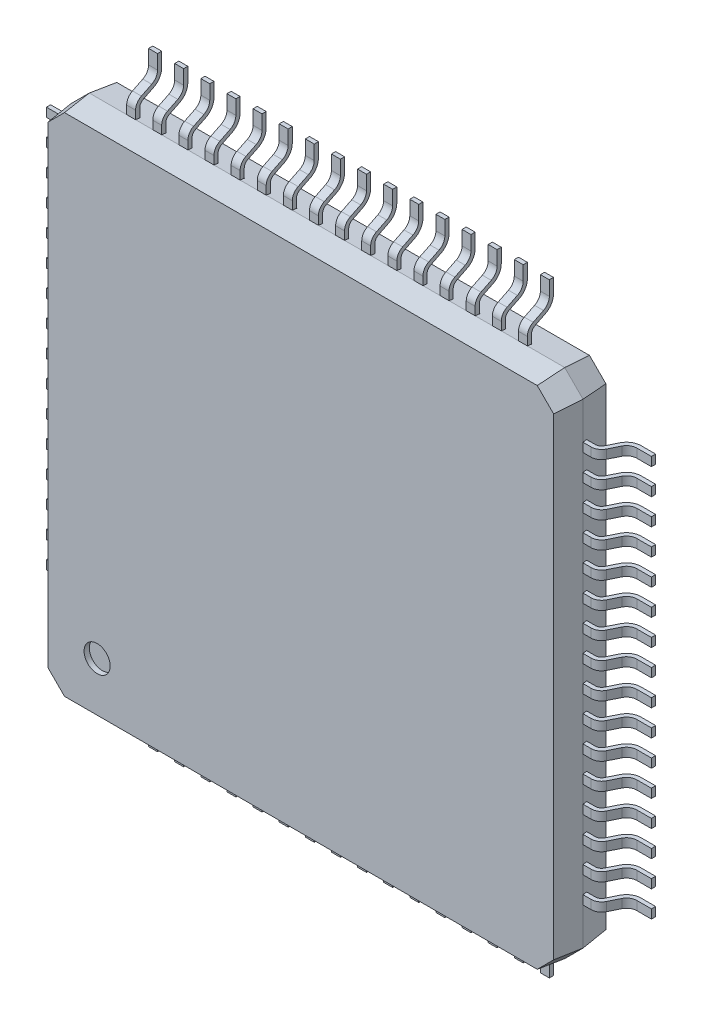
SolidWorks part; units mm, degrees
ref_plane "Front Plane" through (0, 0, 0) normal (0, 0, 1) x (1, 0, 0)
ref_plane "Top Plane" through (0, 0, 0) normal (0, 1, 0) x (1, 0, 0)
ref_plane "Right Plane" through (0, 0, 0) normal (1, 0, 0) x (0, 0, -1)
sketch "Sketch1" plane through (0, 0, 0) normal (0, 0, 1) x (1, 0, 0)
  line L0 (-4.55, 4.9) -> (-4.9, 4.55)
  line L1 (-4.55, 4.9) -> (4.55, 4.9)
  line L2 (-4.9, 4.55) -> (-4.9, -4.55)
  line L3 (-4.55, -4.9) -> (4.55, -4.9)
  line L4 (4.9, 4.55) -> (4.9, -4.55)
  line L5 (-4.9, -4.55) -> (-4.55, -4.9)
  line L6 (4.55, -4.9) -> (4.9, -4.55)
  line L7 (4.55, 4.9) -> (4.9, 4.55)
  point P0 (0, 0)
  point P1 (-4.9, 4.9)
  point P3 (4.9, -4.9)
  point P4 (-4.9, -4.9)
  point P5 (4.9, 4.9)
  dimension "D1" = 0.35
  dimension "D2" = 0.35
  dimension "D3" = 0.35
  dimension "D4" = 0.35
  dimension "D5" = 0.35
  dimension "D6" = 0.35
  dimension "D7" = 0.35
  dimension "D8" = 0.35
extrude "Extrude1" add sketch "Sketch1" along normal blind 1
chamfer "Chamfer1" distance 0.5 angle 7 8 edges at (0, 4.9, 1) (-4.725, 4.725, 1) (-4.9, 0, 1) (-4.725, -4.725, 1) (0, -4.9, 1) (4.725, -4.725, 1) (4.9, 0, 1) (4.725, 4.725, 1)
chamfer "Chamfer4" distance 0.5 angle 7 8 edges at (4.725, -4.725, 0) (4.9, 0, 0) (4.725, 4.725, 0) (0, 4.9, 0) (0, -4.9, 0) (-4.725, -4.725, 0) (-4.725, 4.725, 0) (-4.9, 0, 0)
sketch "Sketch2" plane through (0, 0, 1) normal (0, 0, 1) x (1, 0, 0)
  circle A0 centre (-3.9, -3.9) radius 0.25
extrude "Extrude2" cut sketch "Sketch2" against normal blind 0.1
sketch "Sketch4" plane through (0, 0, 0) normal (0, 0, -1) x (-1, 0, 0)
  line L0 (-3.3358, -4.8899) -> (-3.165, -4.8899)
  line L1 (0, 0) -> (0, 5.3794) construction
  line L2 (-5.7946, 0) -> (6, 0) construction
  line L3 (-3.3358, -4.8899) -> (-3.3358, -5.7873)
  line L4 (-3.3358, -5.7873) -> (-3.165, -5.7873)
  line L5 (-3.165, -4.8899) -> (-3.165, -5.7873)
  line L7 (-2.8358, -4.8899) -> (-2.665, -4.8899)
  line L8 (-2.8358, -4.8899) -> (-2.8358, -5.7873)
  line L9 (-2.8358, -5.7873) -> (-2.665, -5.7873)
  line L10 (-2.665, -4.8899) -> (-2.665, -5.7873)
  line L11 (-2.3358, -4.8899) -> (-2.165, -4.8899)
  line L12 (-2.3358, -4.8899) -> (-2.3358, -5.7873)
  line L13 (-2.3358, -5.7873) -> (-2.165, -5.7873)
  line L14 (-2.165, -4.8899) -> (-2.165, -5.7873)
  line L15 (-1.8358, -4.8899) -> (-1.665, -4.8899)
  line L16 (-1.8358, -4.8899) -> (-1.8358, -5.7873)
  line L17 (-1.8358, -5.7873) -> (-1.665, -5.7873)
  line L18 (-1.665, -4.8899) -> (-1.665, -5.7873)
  line L19 (-1.3358, -4.8899) -> (-1.165, -4.8899)
  line L20 (-1.3358, -4.8899) -> (-1.3358, -5.7873)
  line L21 (-1.3358, -5.7873) -> (-1.165, -5.7873)
  line L22 (-1.165, -4.8899) -> (-1.165, -5.7873)
  line L23 (-0.8358, -4.8899) -> (-0.665, -4.8899)
  line L24 (-0.8358, -4.8899) -> (-0.8358, -5.7873)
  line L25 (-0.8358, -5.7873) -> (-0.665, -5.7873)
  line L26 (-0.665, -4.8899) -> (-0.665, -5.7873)
  line L27 (-0.3358, -4.8899) -> (-0.165, -4.8899)
  line L28 (-0.3358, -4.8899) -> (-0.3358, -5.7873)
  line L29 (-0.3358, -5.7873) -> (-0.165, -5.7873)
  line L30 (-0.165, -4.8899) -> (-0.165, -5.7873)
  line L31 (0.1642, -4.8899) -> (0.335, -4.8899)
  line L32 (0.1642, -4.8899) -> (0.1642, -5.7873)
  line L33 (0.1642, -5.7873) -> (0.335, -5.7873)
  line L34 (0.335, -4.8899) -> (0.335, -5.7873)
  line L35 (0.6642, -4.8899) -> (0.835, -4.8899)
  line L36 (0.6642, -4.8899) -> (0.6642, -5.7873)
  line L37 (0.6642, -5.7873) -> (0.835, -5.7873)
  line L38 (0.835, -4.8899) -> (0.835, -5.7873)
  line L39 (1.1642, -4.8899) -> (1.335, -4.8899)
  line L40 (1.1642, -4.8899) -> (1.1642, -5.7873)
  line L41 (1.1642, -5.7873) -> (1.335, -5.7873)
  line L42 (1.335, -4.8899) -> (1.335, -5.7873)
  line L43 (1.6642, -4.8899) -> (1.835, -4.8899)
  line L44 (1.6642, -4.8899) -> (1.6642, -5.7873)
  line L45 (1.6642, -5.7873) -> (1.835, -5.7873)
  line L46 (1.835, -4.8899) -> (1.835, -5.7873)
  line L47 (2.1642, -4.8899) -> (2.335, -4.8899)
  line L48 (2.1642, -4.8899) -> (2.1642, -5.7873)
  line L49 (2.1642, -5.7873) -> (2.335, -5.7873)
  line L50 (2.335, -4.8899) -> (2.335, -5.7873)
  line L51 (2.6642, -4.8899) -> (2.835, -4.8899)
  line L52 (2.6642, -4.8899) -> (2.6642, -5.7873)
  line L53 (2.6642, -5.7873) -> (2.835, -5.7873)
  line L54 (2.835, -4.8899) -> (2.835, -5.7873)
  line L55 (3.1642, -4.8899) -> (3.335, -4.8899)
  line L56 (3.1642, -4.8899) -> (3.1642, -5.7873)
  line L57 (3.1642, -5.7873) -> (3.335, -5.7873)
  line L58 (3.335, -4.8899) -> (3.335, -5.7873)
  line L59 (3.6642, -4.8899) -> (3.835, -4.8899)
  line L60 (3.6642, -4.8899) -> (3.6642, -5.7873)
  line L61 (3.6642, -5.7873) -> (3.835, -5.7873)
  line L62 (3.835, -4.8899) -> (3.835, -5.7873)
  line L63 (4.8901, -3.3341) -> (5.7911, -3.3341)
  line L64 (5.7911, -3.1641) -> (5.7911, -3.3341)
  line L65 (-3.8358, -4.8899) -> (-3.665, -4.8899)
  line L66 (-3.8358, -4.8899) -> (-3.8358, -5.7873)
  line L67 (-3.8358, -5.7873) -> (-3.665, -5.7873)
  line L68 (-3.665, -4.8899) -> (-3.665, -5.7873)
  line L69 (4.8901, -3.1641) -> (5.7911, -3.1641)
  line L70 (4.8901, -3.1641) -> (4.8901, -3.3341)
  line L71 (4.8901, -2.8341) -> (5.7911, -2.8341)
  line L72 (5.7911, -2.6641) -> (5.7911, -2.8341)
  line L73 (4.8901, -2.6641) -> (5.7911, -2.6641)
  line L74 (4.8901, -2.6641) -> (4.8901, -2.8341)
  line L75 (4.8901, -2.3341) -> (5.7911, -2.3341)
  line L76 (5.7911, -2.1641) -> (5.7911, -2.3341)
  line L77 (4.8901, -2.1641) -> (5.7911, -2.1641)
  line L78 (4.8901, -2.1641) -> (4.8901, -2.3341)
  line L79 (4.8901, -1.8341) -> (5.7911, -1.8341)
  line L80 (5.7911, -1.6641) -> (5.7911, -1.8341)
  line L81 (4.8901, -1.6641) -> (5.7911, -1.6641)
  line L82 (4.8901, -1.6641) -> (4.8901, -1.8341)
  line L83 (4.8901, -1.3341) -> (5.7911, -1.3341)
  line L84 (5.7911, -1.1641) -> (5.7911, -1.3341)
  line L85 (4.8901, -1.1641) -> (5.7911, -1.1641)
  line L86 (4.8901, -1.1641) -> (4.8901, -1.3341)
  line L87 (4.8901, -0.8341) -> (5.7911, -0.8341)
  line L88 (5.7911, -0.6641) -> (5.7911, -0.8341)
  line L89 (4.8901, -0.6641) -> (5.7911, -0.6641)
  line L90 (4.8901, -0.6641) -> (4.8901, -0.8341)
  line L91 (4.8901, -0.3341) -> (5.7911, -0.3341)
  line L92 (5.7911, -0.1641) -> (5.7911, -0.3341)
  line L93 (4.8901, -0.1641) -> (5.7911, -0.1641)
  line L94 (4.8901, -0.1641) -> (4.8901, -0.3341)
  line L95 (4.8901, 0.1659) -> (5.7911, 0.1659)
  line L96 (5.7911, 0.3359) -> (5.7911, 0.1659)
  line L97 (4.8901, 0.3359) -> (5.7911, 0.3359)
  line L98 (4.8901, 0.3359) -> (4.8901, 0.1659)
  line L99 (4.8901, 0.6659) -> (5.7911, 0.6659)
  line L100 (5.7911, 0.8359) -> (5.7911, 0.6659)
  line L101 (4.8901, 0.8359) -> (5.7911, 0.8359)
  line L102 (4.8901, 0.8359) -> (4.8901, 0.6659)
  line L103 (4.8901, 1.1659) -> (5.7911, 1.1659)
  line L104 (5.7911, 1.3359) -> (5.7911, 1.1659)
  line L105 (4.8901, 1.3359) -> (5.7911, 1.3359)
  line L106 (4.8901, 1.3359) -> (4.8901, 1.1659)
  line L107 (4.8901, 1.6659) -> (5.7911, 1.6659)
  line L108 (5.7911, 1.8359) -> (5.7911, 1.6659)
  line L109 (4.8901, 1.8359) -> (5.7911, 1.8359)
  line L110 (4.8901, 1.8359) -> (4.8901, 1.6659)
  line L111 (4.8901, 2.1659) -> (5.7911, 2.1659)
  line L112 (5.7911, 2.3359) -> (5.7911, 2.1659)
  line L113 (4.8901, 2.3359) -> (5.7911, 2.3359)
  line L114 (4.8901, 2.3359) -> (4.8901, 2.1659)
  line L115 (4.8901, 2.6659) -> (5.7911, 2.6659)
  line L116 (5.7911, 2.8359) -> (5.7911, 2.6659)
  line L117 (4.8901, 2.8359) -> (5.7911, 2.8359)
  line L118 (4.8901, 2.8359) -> (4.8901, 2.6659)
  line L119 (4.8901, 3.1659) -> (5.7911, 3.1659)
  line L120 (5.7911, 3.3359) -> (5.7911, 3.1659)
  line L121 (4.8901, 3.3359) -> (5.7911, 3.3359)
  line L122 (4.8901, 3.3359) -> (4.8901, 3.1659)
  line L123 (4.8901, 3.6659) -> (5.7911, 3.6659)
  line L124 (5.7911, 3.8359) -> (5.7911, 3.6659)
  line L125 (4.8901, 3.8359) -> (5.7911, 3.8359)
  line L126 (4.8901, 3.8359) -> (4.8901, 3.6659)
  line L127 (-3.3358, 5.7873) -> (-3.165, 5.7873)
  line L128 (-3.3358, 5.7873) -> (-3.3358, 4.89)
  line L129 (-3.3358, 4.89) -> (-3.165, 4.89)
  line L130 (-3.8358, 5.7873) -> (-3.665, 5.7873)
  line L131 (-3.8358, 5.7873) -> (-3.8358, 4.89)
  line L132 (-3.8358, 4.89) -> (-3.665, 4.89)
  line L133 (-3.665, 5.7873) -> (-3.665, 4.89)
  line L135 (-3.165, 5.7873) -> (-3.165, 4.89)
  line L136 (-2.8358, 5.7873) -> (-2.665, 5.7873)
  line L137 (-2.8358, 5.7873) -> (-2.8358, 4.89)
  line L138 (-2.8358, 4.89) -> (-2.665, 4.89)
  line L139 (-2.665, 5.7873) -> (-2.665, 4.89)
  line L140 (-2.3358, 5.7873) -> (-2.165, 5.7873)
  line L141 (-2.3358, 5.7873) -> (-2.3358, 4.89)
  line L142 (-2.3358, 4.89) -> (-2.165, 4.89)
  line L143 (-2.165, 5.7873) -> (-2.165, 4.89)
  line L144 (-1.8358, 5.7873) -> (-1.665, 5.7873)
  line L145 (-1.8358, 5.7873) -> (-1.8358, 4.89)
  line L146 (-1.8358, 4.89) -> (-1.665, 4.89)
  line L147 (-1.665, 5.7873) -> (-1.665, 4.89)
  line L148 (-1.3358, 5.7873) -> (-1.165, 5.7873)
  line L149 (-1.3358, 5.7873) -> (-1.3358, 4.89)
  line L150 (-1.3358, 4.89) -> (-1.165, 4.89)
  line L151 (-1.165, 5.7873) -> (-1.165, 4.89)
  line L152 (-0.8358, 5.7873) -> (-0.665, 5.7873)
  line L153 (-0.8358, 5.7873) -> (-0.8358, 4.89)
  line L154 (-0.8358, 4.89) -> (-0.665, 4.89)
  line L155 (-0.665, 5.7873) -> (-0.665, 4.89)
  line L156 (-0.3358, 5.7873) -> (-0.165, 5.7873)
  line L157 (-0.3358, 5.7873) -> (-0.3358, 4.89)
  line L158 (-0.3358, 4.89) -> (-0.165, 4.89)
  line L159 (-0.165, 5.7873) -> (-0.165, 4.89)
  line L160 (0.1642, 5.7873) -> (0.335, 5.7873)
  line L161 (0.1642, 5.7873) -> (0.1642, 4.89)
  line L162 (0.1642, 4.89) -> (0.335, 4.89)
  line L163 (0.335, 5.7873) -> (0.335, 4.89)
  line L164 (0.6642, 5.7873) -> (0.835, 5.7873)
  line L165 (0.6642, 5.7873) -> (0.6642, 4.89)
  line L166 (0.6642, 4.89) -> (0.835, 4.89)
  line L167 (0.835, 5.7873) -> (0.835, 4.89)
  line L168 (1.1642, 5.7873) -> (1.335, 5.7873)
  line L169 (1.1642, 5.7873) -> (1.1642, 4.89)
  line L170 (1.1642, 4.89) -> (1.335, 4.89)
  line L171 (1.335, 5.7873) -> (1.335, 4.89)
  line L172 (1.6642, 5.7873) -> (1.835, 5.7873)
  line L173 (1.6642, 5.7873) -> (1.6642, 4.89)
  line L174 (1.6642, 4.89) -> (1.835, 4.89)
  line L175 (1.835, 5.7873) -> (1.835, 4.89)
  line L176 (2.1642, 5.7873) -> (2.335, 5.7873)
  line L177 (2.1642, 5.7873) -> (2.1642, 4.89)
  line L178 (2.1642, 4.89) -> (2.335, 4.89)
  line L179 (2.335, 5.7873) -> (2.335, 4.89)
  line L180 (2.6642, 5.7873) -> (2.835, 5.7873)
  line L181 (2.6642, 5.7873) -> (2.6642, 4.89)
  line L182 (2.6642, 4.89) -> (2.835, 4.89)
  line L183 (2.835, 5.7873) -> (2.835, 4.89)
  line L184 (3.1642, 5.7873) -> (3.335, 5.7873)
  line L185 (3.1642, 5.7873) -> (3.1642, 4.89)
  line L186 (3.1642, 4.89) -> (3.335, 4.89)
  line L187 (3.335, 5.7873) -> (3.335, 4.89)
  line L188 (3.6642, 5.7873) -> (3.835, 5.7873)
  line L189 (3.6642, 5.7873) -> (3.6642, 4.89)
  line L190 (3.6642, 4.89) -> (3.835, 4.89)
  line L191 (3.835, 5.7873) -> (3.835, 4.89)
  line L192 (-5.7899, -3.3341) -> (-4.8889, -3.3341)
  line L193 (-4.8889, -3.1641) -> (-4.8889, -3.3341)
  line L194 (-5.7899, -3.1641) -> (-4.8889, -3.1641)
  line L195 (-5.7899, -3.1641) -> (-5.7899, -3.3341)
  line L196 (-5.7899, -2.8341) -> (-4.8889, -2.8341)
  line L197 (4.8901, -3.8341) -> (5.7911, -3.8341)
  line L198 (5.7911, -3.6641) -> (5.7911, -3.8341)
  line L199 (4.8901, -3.6641) -> (5.7911, -3.6641)
  line L200 (4.8901, -3.6641) -> (4.8901, -3.8341)
  line L201 (-4.8889, -2.6641) -> (-4.8889, -2.8341)
  line L202 (-5.7899, -2.6641) -> (-4.8889, -2.6641)
  line L203 (-5.7899, -2.6641) -> (-5.7899, -2.8341)
  line L204 (-5.7899, -2.3341) -> (-4.8889, -2.3341)
  line L205 (-4.8889, -2.1641) -> (-4.8889, -2.3341)
  line L206 (-5.7899, -2.1641) -> (-4.8889, -2.1641)
  line L207 (-5.7899, -2.1641) -> (-5.7899, -2.3341)
  line L208 (-5.7899, -1.8341) -> (-4.8889, -1.8341)
  line L209 (-4.8889, -1.6641) -> (-4.8889, -1.8341)
  line L210 (-5.7899, -1.6641) -> (-4.8889, -1.6641)
  line L211 (-5.7899, -1.6641) -> (-5.7899, -1.8341)
  line L212 (-5.7899, -1.3341) -> (-4.8889, -1.3341)
  line L213 (-4.8889, -1.1641) -> (-4.8889, -1.3341)
  line L214 (-5.7899, -1.1641) -> (-4.8889, -1.1641)
  line L215 (-5.7899, -1.1641) -> (-5.7899, -1.3341)
  line L216 (-5.7899, -0.8341) -> (-4.8889, -0.8341)
  line L217 (-4.8889, -0.6641) -> (-4.8889, -0.8341)
  line L218 (-5.7899, -0.6641) -> (-4.8889, -0.6641)
  line L219 (-5.7899, -0.6641) -> (-5.7899, -0.8341)
  line L220 (-5.7899, -0.3341) -> (-4.8889, -0.3341)
  line L221 (-4.8889, -0.1641) -> (-4.8889, -0.3341)
  line L222 (-5.7899, -0.1641) -> (-4.8889, -0.1641)
  line L223 (-5.7899, -0.1641) -> (-5.7899, -0.3341)
  line L224 (-5.7899, 0.1659) -> (-4.8889, 0.1659)
  line L225 (-4.8889, 0.3359) -> (-4.8889, 0.1659)
  line L226 (-5.7899, 0.3359) -> (-4.8889, 0.3359)
  line L227 (-5.7899, 0.3359) -> (-5.7899, 0.1659)
  line L228 (-5.7899, 0.6659) -> (-4.8889, 0.6659)
  line L229 (-4.8889, 0.8359) -> (-4.8889, 0.6659)
  line L230 (-5.7899, 0.8359) -> (-4.8889, 0.8359)
  line L231 (-5.7899, 0.8359) -> (-5.7899, 0.6659)
  line L232 (-5.7899, 1.1659) -> (-4.8889, 1.1659)
  line L233 (-4.8889, 1.3359) -> (-4.8889, 1.1659)
  line L234 (-5.7899, 1.3359) -> (-4.8889, 1.3359)
  line L235 (-5.7899, 1.3359) -> (-5.7899, 1.1659)
  line L236 (-5.7899, 1.6659) -> (-4.8889, 1.6659)
  line L237 (-4.8889, 1.8359) -> (-4.8889, 1.6659)
  line L238 (-5.7899, 1.8359) -> (-4.8889, 1.8359)
  line L239 (-5.7899, 1.8359) -> (-5.7899, 1.6659)
  line L240 (-5.7899, 2.1659) -> (-4.8889, 2.1659)
  line L241 (-4.8889, 2.3359) -> (-4.8889, 2.1659)
  line L242 (-5.7899, 2.3359) -> (-4.8889, 2.3359)
  line L243 (-5.7899, 2.3359) -> (-5.7899, 2.1659)
  line L244 (-5.7899, 2.6659) -> (-4.8889, 2.6659)
  line L245 (-4.8889, 2.8359) -> (-4.8889, 2.6659)
  line L246 (-5.7899, 2.8359) -> (-4.8889, 2.8359)
  line L247 (-5.7899, 2.8359) -> (-5.7899, 2.6659)
  line L248 (-5.7899, 3.1659) -> (-4.8889, 3.1659)
  line L249 (-4.8889, 3.3359) -> (-4.8889, 3.1659)
  line L250 (-5.7899, 3.3359) -> (-4.8889, 3.3359)
  line L251 (-5.7899, 3.3359) -> (-5.7899, 3.1659)
  line L252 (-5.7899, 3.6659) -> (-4.8889, 3.6659)
  line L253 (-4.8889, 3.8359) -> (-4.8889, 3.6659)
  line L254 (-5.7899, 3.8359) -> (-4.8889, 3.8359)
  line L255 (-5.7899, 3.8359) -> (-5.7899, 3.6659)
  line L261 (-5.7899, -3.8341) -> (-4.8889, -3.8341)
  line L262 (-4.8889, -3.6641) -> (-4.8889, -3.8341)
  line L263 (-5.7899, -3.6641) -> (-4.8889, -3.6641)
  line L264 (-5.7899, -3.6641) -> (-5.7899, -3.8341)
extrude "Extrude3" add sketch "Sketch4" against normal blind 0.5 separate body
sketch "Sketch8" plane through (0, -3.8341, 0) normal (0, -1, 0) x (1, 0, 0)
  line L0 (5.0567, 0.5) -> (5.7899, 0.5)
  line L1 (5.7899, 0.5) -> (5.7899, 0.08)
  line L2 (5.7899, 0.5) -> (5.7899, 0) construction
  line L3 (5.7899, 0.08) -> (5.5128, 0.08)
  line L9 (5.0567, 0.42) -> (4.8902, 0.42)
  line L10 (4.8386, 0) -> (5.5128, 0)
  line L11 (4.8902, 0.42) -> (4.8386, 0)
  line L12 (5.3335, 0.1914) -> (5.236, 0.3886)
  line L14 (5.2618, 0.1559) -> (5.1643, 0.3532)
  arc A4 (5.5128, 0) -> (5.2618, 0.1559) centre (5.5128, 0.28) cw
  arc A5 (5.0567, 0.42) -> (5.1643, 0.3532) centre (5.0567, 0.3) cw
  arc A6 (5.5128, 0.08) -> (5.3335, 0.1914) centre (5.5128, 0.28) cw
  arc A7 (5.0567, 0.5) -> (5.236, 0.3886) centre (5.0567, 0.3) cw
sketch "Sketch14" plane through (3.8358, 0, 0) normal (1, 0, 0) x (0, 0, -1)
  line L0 (-0.5, -5.0567) -> (-0.5, -5.7873)
  line L1 (-0.5, -5.7873) -> (-0.08, -5.7873)
  line L2 (-0.1559, -5.2618) -> (-0.3532, -5.1643)
  line L3 (-0.08, -5.7873) -> (-0.08, -5.5128)
  line L4 (-0.1914, -5.3335) -> (-0.3886, -5.236)
  line L5 (-0.42, -4.8902) -> (-0.4124, -4.8892)
  line L6 (-0.5, -4.9) -> (0, -4.8386) construction
  line L7 (-0.42, -5.0567) -> (-0.42, -4.8902)
  line L8 (-0.4124, -4.8892) -> (0, -4.8899)
  line L9 (0, -4.8899) -> (0, -5.5128)
  arc A0 (-0.5, -5.0567) -> (-0.3886, -5.236) centre (-0.3, -5.0567) ccw
  arc A1 (-0.08, -5.5128) -> (-0.1914, -5.3335) centre (-0.28, -5.5128) ccw
  arc A2 (-0.42, -5.0567) -> (-0.3532, -5.1643) centre (-0.3, -5.0567) ccw
  arc A3 (0, -5.5128) -> (-0.1559, -5.2618) centre (-0.28, -5.5128) ccw
extrude "Extrude9" cut sketch "Sketch14" against normal through all
sketch "Sketch15" plane through (0, -3.8341, 0) normal (0, -1, 0) x (1, 0, 0)
  line L0 (5.0567, 0.5) -> (5.7899, 0.5)
  line L1 (5.7899, 0.5) -> (5.7899, 0.08)
  line L2 (5.7899, 0.08) -> (5.5128, 0.08)
  line L3 (5.0567, 0.42) -> (4.8902, 0.42)
  line L4 (4.8902, 0.42) -> (4.8885, 0.406)
  line L5 (4.8902, 0.42) -> (4.8386, 0) construction
  line L6 (5.3335, 0.1914) -> (5.236, 0.3886)
  line L7 (5.2618, 0.1559) -> (5.1643, 0.3532)
  line L8 (4.8885, 0.406) -> (4.8889, 0)
  line L9 (4.8889, 0) -> (5.5128, 0)
  arc A0 (5.5128, 0) -> (5.2618, 0.1559) centre (5.5128, 0.28) cw
  arc A1 (5.0567, 0.42) -> (5.1643, 0.3532) centre (5.0567, 0.3) cw
  arc A2 (5.5128, 0.08) -> (5.3335, 0.1914) centre (5.5128, 0.28) cw
  arc A3 (5.0567, 0.5) -> (5.236, 0.3886) centre (5.0567, 0.3) cw
extrude "Extrude10" cut sketch "Sketch15" against normal through all
sketch "Sketch16" plane through (3.8358, 0, 0) normal (1, 0, 0) x (0, 0, -1)
  line L0 (-0.5, 5.0578) -> (-0.5, 5.791)
  line L1 (-0.5, 5.791) -> (-0.08, 5.791)
  line L2 (-0.08, 5.791) -> (-0.08, 5.5139)
  line L3 (-0.42, 5.0578) -> (-0.42, 4.8912)
  line L4 (-0.42, 4.8912) -> (-0.406, 4.8895)
  line L5 (-0.1914, 5.3346) -> (-0.3886, 5.2371)
  line L6 (-0.1559, 5.2629) -> (-0.3532, 5.1653)
  line L7 (-0.406, 4.8895) -> (0, 4.89)
  line L8 (0, 4.89) -> (0, 5.5139)
  arc A0 (0, 5.5139) -> (-0.1559, 5.2629) centre (-0.28, 5.5139) cw
  arc A1 (-0.42, 5.0578) -> (-0.3532, 5.1653) centre (-0.3, 5.0578) cw
  arc A2 (-0.08, 5.5139) -> (-0.1914, 5.3346) centre (-0.28, 5.5139) cw
  arc A3 (-0.5, 5.0578) -> (-0.3886, 5.2371) centre (-0.3, 5.0578) cw
extrude "Extrude11" cut sketch "Sketch16" against normal through all
sketch "Sketch17" plane through (0, 3.8359, 0) normal (0, 1, 0) x (1, 0, 0)
  line L0 (-5.0579, -0.5) -> (-5.7911, -0.5)
  line L1 (-5.7911, -0.5) -> (-5.7911, -0.08)
  line L2 (-5.7911, -0.08) -> (-5.514, -0.08)
  line L3 (-5.0579, -0.42) -> (-4.8913, -0.42)
  line L4 (-4.8913, -0.42) -> (-4.8896, -0.406)
  line L5 (-5.3347, -0.1914) -> (-5.2372, -0.3886)
  line L6 (-5.263, -0.1559) -> (-5.1654, -0.3532)
  line L7 (-4.8896, -0.406) -> (-4.8901, 0)
  line L8 (-4.8901, 0) -> (-5.514, 0)
  arc A0 (-5.514, 0) -> (-5.263, -0.1559) centre (-5.514, -0.28) cw
  arc A1 (-5.0579, -0.42) -> (-5.1654, -0.3532) centre (-5.0579, -0.3) cw
  arc A2 (-5.514, -0.08) -> (-5.3347, -0.1914) centre (-5.514, -0.28) cw
  arc A3 (-5.0579, -0.5) -> (-5.2372, -0.3886) centre (-5.0579, -0.3) cw
extrude "Extrude12" cut sketch "Sketch17" against normal through all
